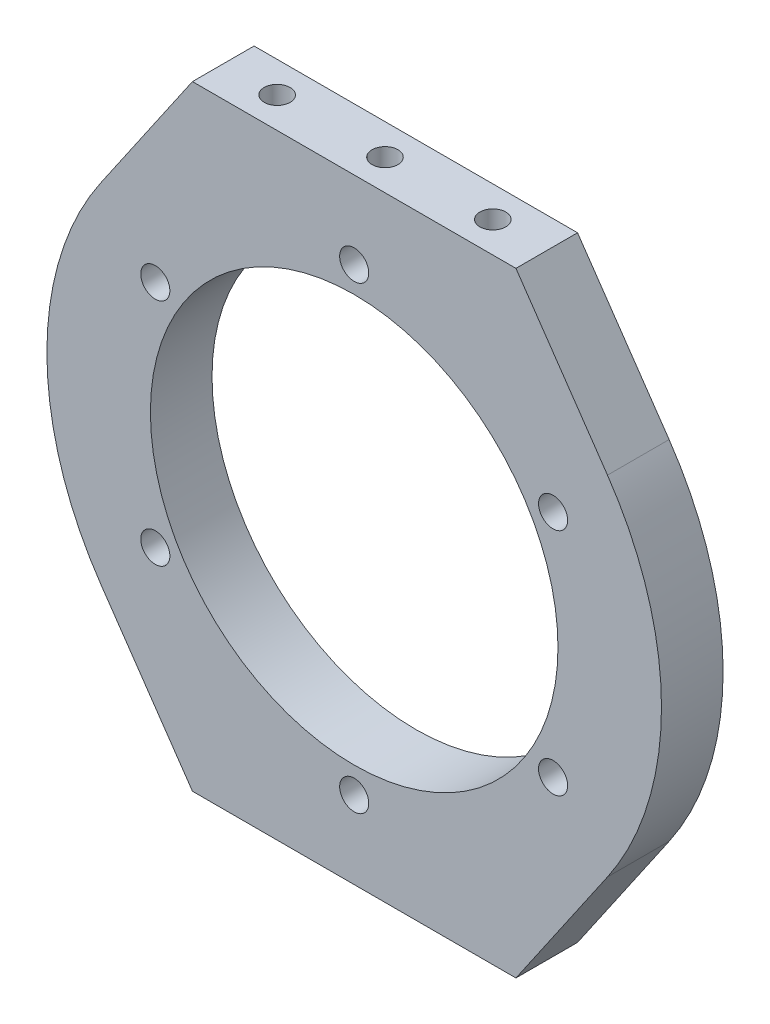
SolidWorks part; units mm, degrees
ref_plane "Front Plane" through (0, 0, 0) normal (0, 0, 1) x (1, 0, 0)
ref_plane "Top Plane" through (0, 0, 0) normal (0, 1, 0) x (1, 0, 0)
ref_plane "Right Plane" through (0, 0, 0) normal (1, 0, 0) x (0, 0, -1)
sketch "Sketch1" plane through (0, 0, 0) normal (0, 0, 1) x (1, 0, 0)
  line L0 (0, 52) -> (0, -52) construction
  line L1 (-47.5, 0) -> (47.5, 0) construction
  line L2 (-25, 47.5) -> (25, 47.5)
  line L3 (-39.154, 26.8926) -> (-25, 47.5)
  line L4 (0, 52) -> (0, 47.5) construction
  line L5 (39.154, 26.8926) -> (25, 47.5)
  line L6 (39.154, -26.8926) -> (25, -47.5)
  line L7 (-25, -47.5) -> (25, -47.5)
  line L8 (-39.154, -26.8926) -> (-25, -47.5)
  arc A0 (-39.154, 26.8926) -> (-39.154, -26.8926) centre (0, 0) ccw
  arc A1 (39.154, -26.8926) -> (39.154, 26.8926) centre (0, 0) ccw
  dimension "D1" = 95
  dimension "D2" = 50
  dimension "D3" = 47.5
extrude "Boss-Extrude1" add sketch "Sketch1" against normal blind 9.525
sketch "Sketch2" plane through (0, 0, 0) normal (0, 0, 1) x (1, 0, 0)
  circle A2 centre (0, 0) radius 35.5 construction
  point P93 (0, 35.5)
  point P95 (59.233, 29.0385)
  point P98 (0, 35.5)
  point P105 (30.7439, 17.75)
  point P106 (30.7439, -17.75)
  point P107 (0, -35.5)
  point P108 (-30.7439, -17.75)
  point P109 (-30.7439, 17.75)
  dimension "D1" = 71
hole_wizard "M4 Clearance Hole1" positions "Sketch2" profile "Sketch3" hole size "M4" standard "ANSI Metric" end condition through all
sketch "Sketch3" plane through (-30.7439, 17.75, 0) normal (1, 0, 0) x (0, -1, 0)
  line L0 (0, 0) -> (0, 9.525)
  line L1 (0, 9.525) -> (2.25, 9.525)
  line L2 (2.25, 9.525) -> (2.25, 0)
  line L5 (2.25, 0) -> (0, 0)
  line L11 (0, -6.35) -> (0, 107.95) construction
  dimension "Thru Hole Dia." = 4.5
  dimension "Thru Hole Depth" = 9.525
sketch "Sketch4" plane through (0, 0, -9.525) normal (0, 0, -1) x (-1, 0, 0)
  circle A0 centre (0, 0) radius 31.5
  dimension "D1" = 63
extrude "Cut-Extrude1" cut sketch "Sketch4" against normal through all
sketch "Sketch5" plane through (0, -47.5, 0) normal (0, -1, 0) x (1, 0, 0)
  point P0 (0, -4.7625)
  point P1 (16.67, -4.7625)
  point P2 (-16.67, -4.7625)
  dimension "D1" = 4.7625
  dimension "D2" = 16.67
  dimension "D3" = 16.67
sketch "Sketch6" plane through (0, 47.5, 0) normal (0, 1, 0) x (1, 0, 0)
  point P0 (16.67, 4.7625)
  point P2 (0, 4.7625)
  point P4 (-16.67, 4.7625)
hole_wizard "Ø4.0mm Dowel Hole1" positions "Sketch6" profile "Sketch7" hole size "Ø4.0" standard "ANSI Metric"
sketch "Sketch7" plane through (16.67, 47.5, -4.7625) normal (1, 0, 0) x (0, 0, 1)
  line L0 (0, 0) -> (0, 4.4017)
  line L1 (0, 4.4017) -> (2, 3.2)
  line L2 (2, 3.2) -> (2, 0)
  line L5 (2, 0) -> (0, 0)
  line L10 (0, 4.4017) -> (-2, 3.2) construction
  line L11 (0, -6.35) -> (0, 107.95) construction
  dimension "Hole Dia." = 4
  dimension "Hole Depth" = 3.2
  dimension "Drill Angle" = 118
hole_wizard "Ø4.0mm Dowel Hole2" positions "Sketch5" profile "Sketch8" hole size "Ø4.0" standard "ANSI Metric"
sketch "Sketch8" plane through (0, -47.5, -4.7625) normal (1, 0, 0) x (0, 0, -1)
  line L0 (0, 0) -> (0, 4.4017)
  line L1 (0, 4.4017) -> (2, 3.2)
  line L2 (2, 3.2) -> (2, 0)
  line L5 (2, 0) -> (0, 0)
  line L10 (0, 4.4017) -> (-2, 3.2) construction
  line L11 (0, -6.35) -> (0, 107.95) construction
  dimension "Hole Dia." = 4
  dimension "Hole Depth" = 3.2
  dimension "Drill Angle" = 118
